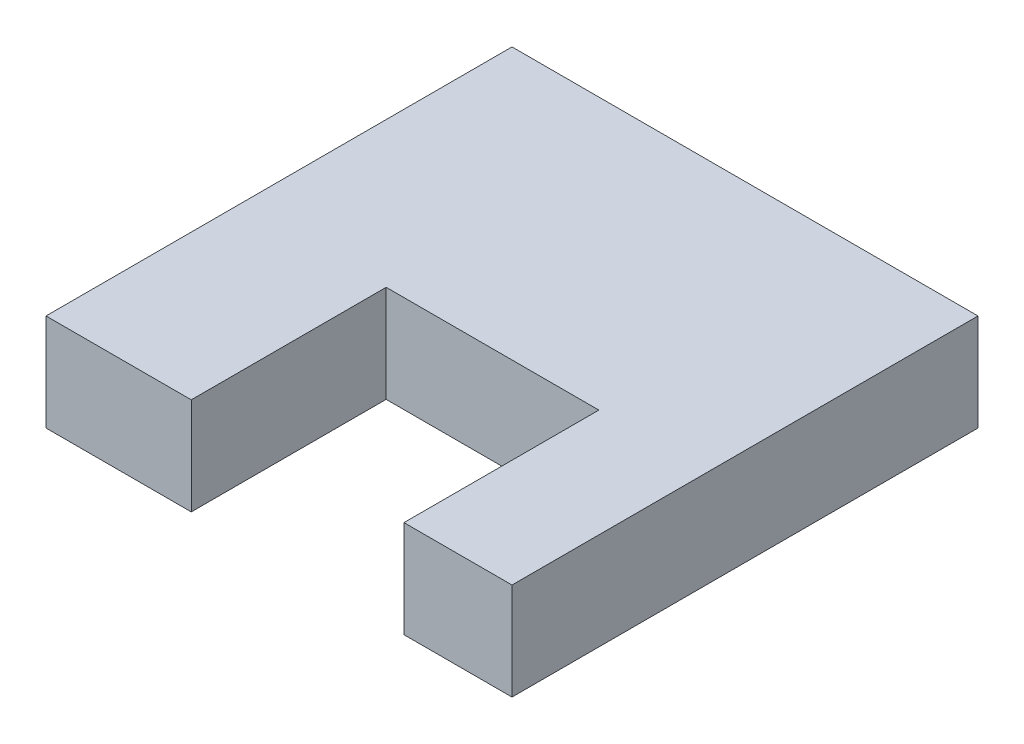
SolidWorks part; units mm, degrees
ref_plane "Front Plane" through (0, 0, 0) normal (0, 0, 1) x (1, 0, 0)
ref_plane "Top Plane" through (0, 0, 0) normal (0, 1, 0) x (1, 0, 0)
ref_plane "Right Plane" through (0, 0, 0) normal (1, 0, 0) x (0, 0, -1)
sketch "Sketch1" plane through (0, 0, 0) normal (0, 1, 0) x (1, 0, 0)
  line L0 (-60, -60) -> (-22.5933, -60)
  line L2 (-60, -60) -> (-60, 60)
  line L3 (-60, 60) -> (60, 60)
  line L4 (60, -60) -> (60, 60)
  line L5 (-60, -60) -> (60, 60) construction
  line L6 (-60, 60) -> (60, -60) construction
  line L7 (-22.5933, -60) -> (-22.5933, -9.8125)
  line L8 (-22.5933, -9.8125) -> (32.1773, -9.8125)
  line L9 (32.1773, -9.8125) -> (32.1773, -60)
  line L10 (32.1773, -60) -> (60, -60)
  point P0 (0, 0)
  point P6 (32.1773, -10.8864)
  point P11 (-22.5933, -9.8125)
  dimension "D1" = 120
  dimension "D2" = 120
extrude "Boss-Extrude1" add sketch "Sketch1" along normal blind 25
